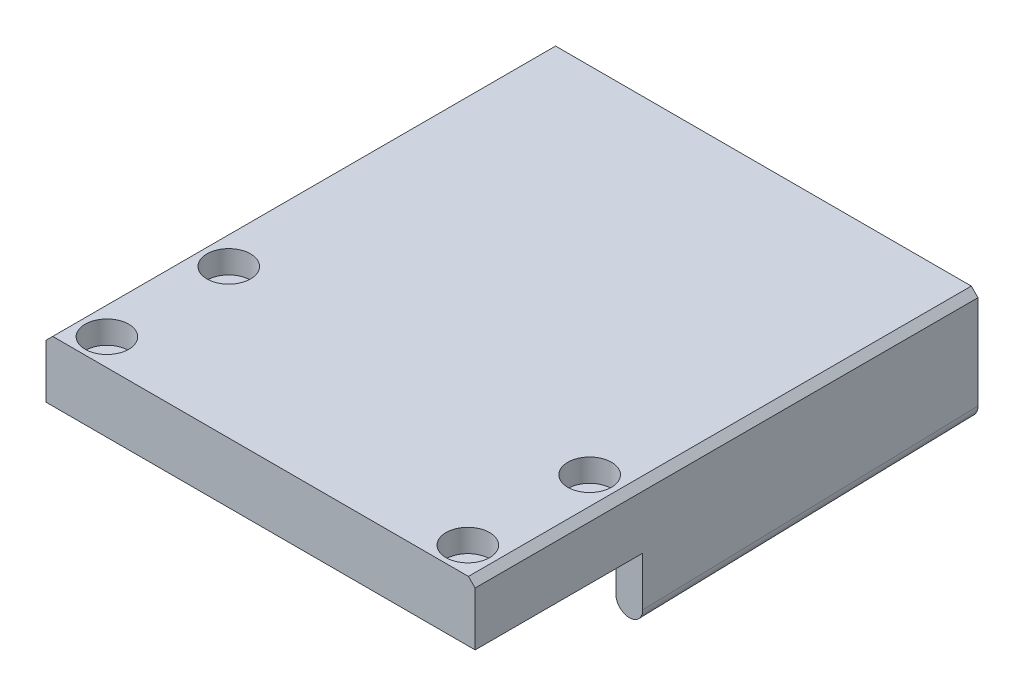
SolidWorks part; units mm, degrees
ref_plane "Front Plane" through (0, 0, 0) normal (0, 0, 1) x (1, 0, 0)
ref_plane "Top Plane" through (0, 0, 0) normal (0, 1, 0) x (1, 0, 0)
ref_plane "Right Plane" through (0, 0, 0) normal (1, 0, 0) x (0, 0, -1)
sketch "Sketch1" plane through (0, 0, 0) normal (0, 1, 0) x (1, 0, 0)
  line L0 (32, -75) -> (-32, -75)
  line L1 (0, -75) -> (0, -150) construction
  line L2 (32, -150) -> (-32, -150)
  line L3 (-32, -150) -> (-32, -75)
  line L4 (32, -150) -> (32, -75)
  point P7 (0, 0)
  dimension "\"neck length" = 75
extrude "Boss-Extrude1" add sketch "Sketch1" along normal blind 19
sketch "Sketch4" plane through (0, 0, 0) normal (1, 0, 0) x (0, 0, -1)
  line L0 (-150, 0) -> (0, 0)
  line L1 (0, 0) -> (-75, 2)
  line L2 (-75, 19) -> (-75, 0) construction
  line L4 (-75, 2) -> (-150, 0)
extrude "Cut-Extrude1" cut sketch "Sketch4" against normal through all both and the other way through all
shell "Shell1" thickness 4 removed face at (0, 1, 112.5)
fillet "Fillet2" 2 edges at (32, 1, 112.5) (28, 1, 112.5) type full round first side face at (32, 10, 112.5) second side face at (28, 5.5, 112.5) middle face at (0, 1, 112.5)
fillet "Fillet3" 2 edges at (-32, 1, 112.5) (-28, 1, 112.5) type full round first side face at (-32, 10, 112.5) second side face at (-28, 5.5, 112.5) middle face at (0, 1, 112.5)
chamfer "Chamfer1" distance 1 angle 45 2 edges at (32, 19, 112.5) (-32, 19, 112.5)
sketch "Sketch7" plane through (0, 0, 150) normal (0, 0, 1) x (1, 0, 0)
  line L1 (-32, 10.0004) -> (32, 10.0004)
  line L2 (-32, 18) -> (-32, 2.0007) construction
  line L3 (32, 18) -> (32, 2.0007) construction
  line L4 (32, 10.0004) -> (32, 0)
  line L7 (-32, 0) -> (-32, 10.0004)
  line L8 (-32, 0) -> (32, 0)
extrude "Cut-Extrude3" cut sketch "Sketch7" against normal blind 25
hole_wizard "CBORE for M3 Hex Socket Head Cap Screw1" positions "Sketch12" profile "Sketch13" counterbore size "M3" standard "ISO" end condition through all
sketch "Sketch12" plane through (75.2969, 19, 61.2992) normal (0, 1, 0) x (1, 0, 0)
  point P0 (-102.2096, -66.5318)
  point P1 (-102.2096, -84.7008)
  point P2 (-48.3841, -84.7008)
  point P3 (-48.3841, -66.5318)
sketch "Sketch13" plane through (-26.9127, 19, 127.831) normal (1, 0, 0) x (0, 0, 1)
  line L0 (0, 0) -> (0, 18.3333)
  line L1 (0, 18.3333) -> (1.45, 18.3333)
  line L2 (1.45, 18.3333) -> (1.45, 3.4)
  line L3 (1.45, 3.4) -> (3.25, 3.4)
  line L4 (3.25, 3.4) -> (3.25, 0)
  line L5 (3.25, 0) -> (0, 0)
  line L6 (0, -6.35) -> (0, 107.95) construction
  dimension "Thru Hole Dia." = 2.9
  dimension "Thru Hole Depth" = 18.3333
  dimension "C'Bore Dia." = 6.5
  dimension "C'Bore Depth" = 3.4
ref_plane "Plane1" through (0, 0, 100) normal (0, 0, 1) x (1, 0, 0)
equation "\"neck length\"= 200mm"
equation "\"stringLength\"=69.2489"
